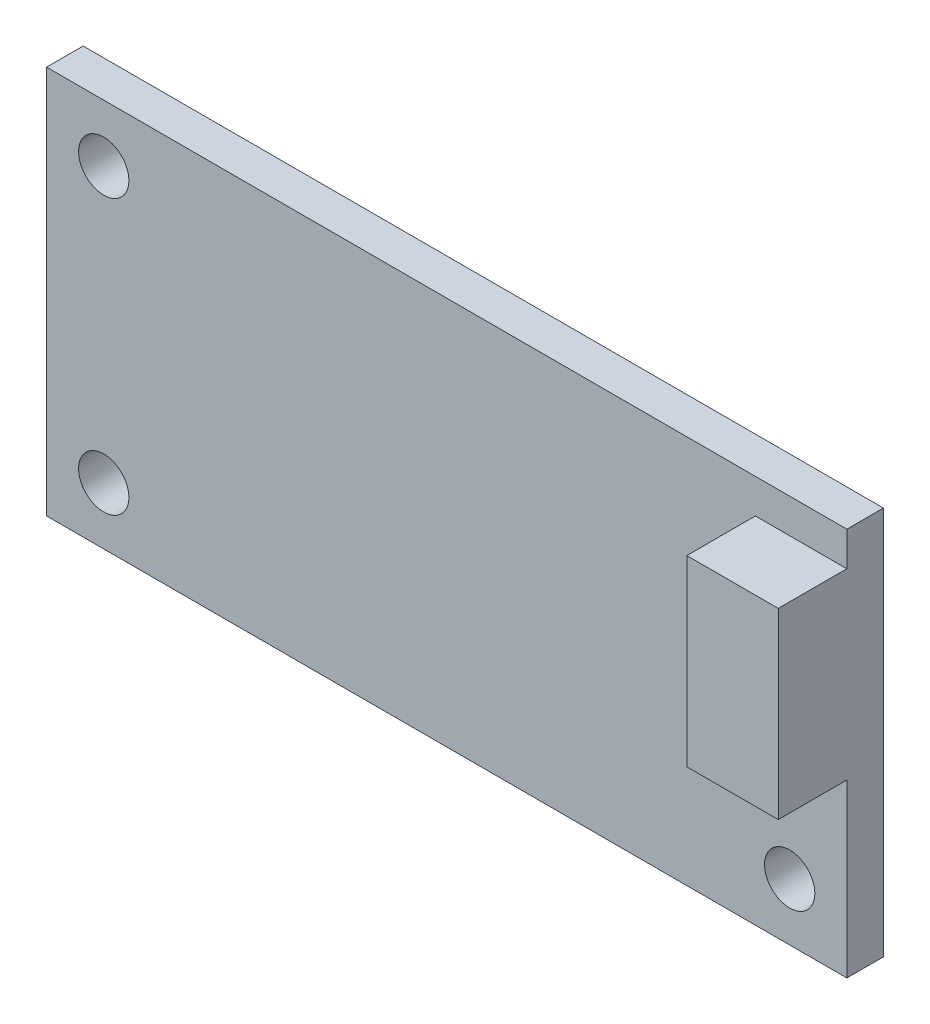
SolidWorks part; units mm, degrees
ref_plane "Front Plane" through (0, 0, 0) normal (0, 0, 1) x (1, 0, 0)
ref_plane "Top Plane" through (0, 0, 0) normal (0, 1, 0) x (1, 0, 0)
ref_plane "Right Plane" through (0, 0, 0) normal (1, 0, 0) x (0, 0, -1)
sketch "Sketch1" plane through (0, 0, 0) normal (0, 0, 1) x (1, 0, 0)
  line L1 (-17.5, 8.5) -> (17.5, 8.5)
  line L2 (-17.5, 8.5) -> (-17.5, -8.5)
  line L3 (-17.5, -8.5) -> (17.5, -8.5)
  line L4 (17.5, 8.5) -> (17.5, -8.5)
  line L5 (-17.5, 8.5) -> (17.5, -8.5) construction
  line L6 (-17.5, -8.5) -> (17.5, 8.5) construction
  point P0 (0, 0)
  dimension "D1" = 17
  dimension "D2" = 35
extrude "Boss-Extrude1" add sketch "Sketch1" along normal blind 1.6
sketch "Sketch2" plane through (0, 0, 1.6) normal (0, 0, 1) x (1, 0, 0)
  line L0 (-17.5, 8.5) -> (-17.5, -8.5) construction
  line L1 (-17.5, -8.5) -> (17.5, -8.5) construction
  line L2 (17.5, 8.5) -> (-17.5, 8.5) construction
  line L3 (17.5, -8.5) -> (17.5, 8.5) construction
  circle A0 centre (-15, -6) radius 1.1
  circle A1 centre (-15, 6) radius 1.1
  circle A2 centre (15, -6) radius 1.1
  dimension "D3" = 2.2
  dimension "D1" = 2.5
  dimension "D2" = 2.5
  dimension "D4" = 2.5
  dimension "D5" = 2.5
extrude "Cut-Extrude1" cut sketch "Sketch2" against normal up to surface (1.6 mm away) up to face at (0, 0, 0)
sketch "Sketch3" plane through (0, 0, 1.6) normal (0, 0, 1) x (1, 0, 0)
  line L0 (17.5, 8.5) -> (-17.5, 8.5) construction
  line L1 (17.5, 7) -> (13.5, 7)
  line L2 (17.5, 7) -> (17.5, -1)
  line L3 (17.5, -1) -> (13.5, -1)
  line L4 (13.5, 7) -> (13.5, -1)
  line L5 (17.5, -8.5) -> (17.5, 8.5) construction
  dimension "D1" = 1.5
  dimension "D2" = 8
  dimension "D3" = 4
extrude "Boss-Extrude2" add sketch "Sketch3" along normal blind 3
